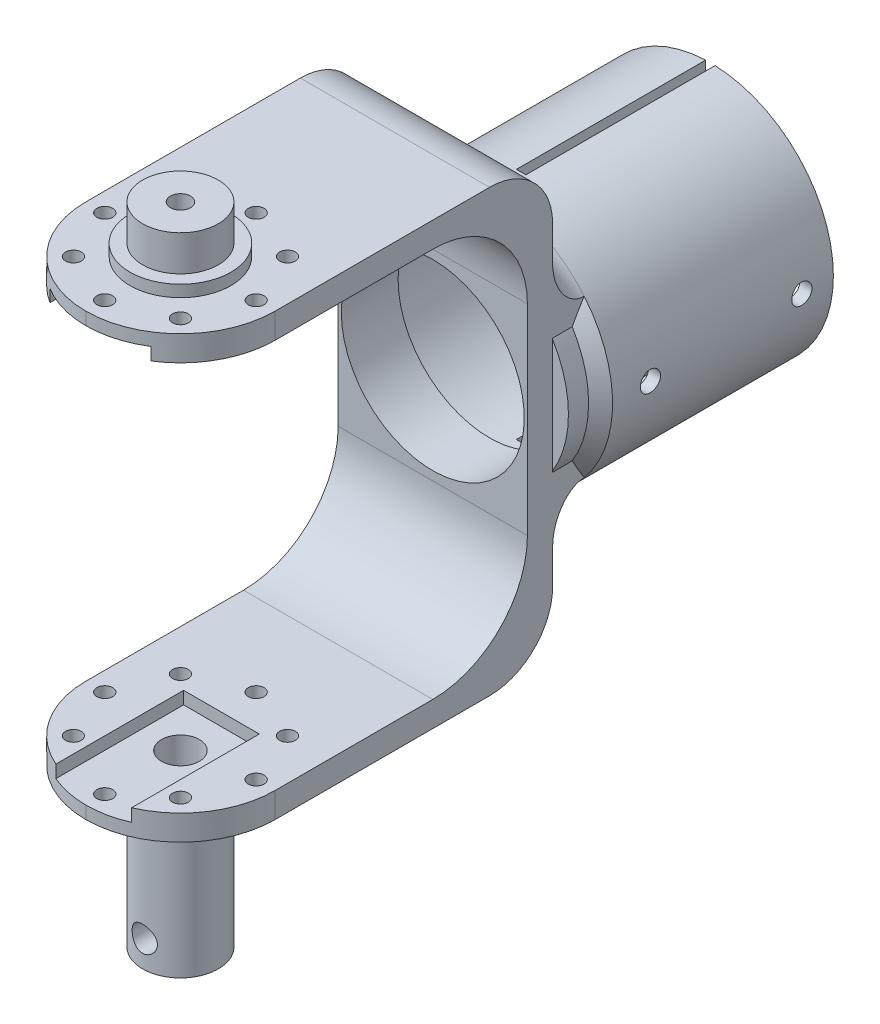
SolidWorks part; units mm, degrees
ref_plane "前视基准面" through (0, 0, 0) normal (0, 0, 1) x (1, 0, 0)
ref_plane "上视基准面" through (0, 0, 0) normal (0, 1, 0) x (1, 0, 0)
ref_plane "右视基准面" through (0, 0, 0) normal (1, 0, 0) x (0, 0, -1)
sketch "草图1" plane through (0, 0, 0) normal (1, 0, 0) x (0, 0, -1)
  line L0 (-27.5, 34.9) -> (31.5, 34.9)
  line L1 (-27.5, 30.9) -> (27.5, 30.9)
  line L2 (31.5, 34.9) -> (31.5, -34.9)
  line L3 (-27.5, -30.9) -> (27.5, -30.9)
  line L4 (27.5, 30.9) -> (27.5, -30.9)
  line L5 (-27.5, 30.9) -> (27.5, -30.9) construction
  line L6 (-27.5, -30.9) -> (27.5, 30.9) construction
  line L7 (-27.5, -34.9) -> (31.5, -34.9)
  line L8 (-27.5, 34.9) -> (-27.5, 30.9)
  line L9 (-27.5, -30.9) -> (-27.5, -34.9)
  point P0 (0, 0)
  dimension "D1" = 61.8
  dimension "D2" = 55
  dimension "D4" = 55
  dimension "D3" = 4
extrude "凸台-拉伸1" add sketch "草图1" along normal blind 30
sketch "草图4" plane through (0, 34.9, 0) normal (0, 1, 0) x (1, 0, 0)
  line L0 (30, 31.5) -> (30, -27.5) construction
  line L1 (30, -27.5) -> (0, -27.5) construction
  circle A0 centre (15, -12.5) radius 12 construction
  circle A1 centre (15, -0.5) radius 1.25
  circle A2 centre (15, -12.5) radius 12 construction
  circle A3 centre (23.4853, -4.0147) radius 1.25
  circle A4 centre (15, -12.5) radius 12 construction
  circle A5 centre (27, -12.5) radius 1.25
  circle A6 centre (15, -12.5) radius 12 construction
  circle A7 centre (23.4853, -20.9853) radius 1.25
  circle A8 centre (15, -12.5) radius 12 construction
  circle A9 centre (15, -24.5) radius 1.25
  circle A10 centre (15, -12.5) radius 12 construction
  circle A11 centre (6.5147, -20.9853) radius 1.25
  circle A12 centre (15, -12.5) radius 12 construction
  circle A13 centre (3, -12.5) radius 1.25
  circle A14 centre (15, -12.5) radius 12 construction
  circle A15 centre (6.5147, -4.0147) radius 1.25
  circle A16 centre (15, -12.5) radius 1.6
  point P31 (15, -12.5)
  dimension "D2" = 15
  dimension "D3" = 24
  dimension "D4" = 2.5
  dimension "D6" = 3.2
  dimension "D1" = 15
  dimension "D5" = 8
extrude "切除-拉伸1" cut sketch "草图4" against normal through all
fillet "圆角1" radius 15 6 edges at (0, 32.9, 27.5) (30, 32.9, 27.5) (30, -32.9, 27.5) (0, -32.9, 27.5) (15, -30.9, -27.5) (15, 30.9, -27.5)
fillet "圆角2" radius 10 2 edges at (15, -34.9, -31.5) (15, 34.9, -31.5)
sketch "草图5" plane through (0, 0, -31.5) normal (0, 0, -1) x (-1, 0, 0)
  line L0 (-30, -24.9) -> (-30, 24.9) construction
  circle A0 centre (-15, 0) radius 17.6
  circle A1 centre (-15, 0) radius 19.5
  dimension "D2" = 35.2
  dimension "D3" = 39
  dimension "D1" = 15
extrude "凸台-拉伸2" add sketch "草图5" along normal blind 40
sketch "草图7" plane through (0, 0, -71.5) normal (0, 0, -1) x (-1, 0, 0)
  line L1 (-15.75, 42.3131) -> (-14.25, 42.3131)
  line L2 (-15.75, 42.3131) -> (-15.75, -42.3131)
  line L3 (-15.75, -42.3131) -> (-14.25, -42.3131)
  line L4 (-14.25, 42.3131) -> (-14.25, -42.3131)
  line L5 (-15.75, 42.3131) -> (-14.25, -42.3131) construction
  line L6 (-15.75, -42.3131) -> (-14.25, 42.3131) construction
  point P0 (-15, 0)
  dimension "D1" = 1.5
extrude "切除-拉伸3" cut sketch "草图7" against normal blind 30
sketch "草图8" plane through (0, 0, 0) normal (1, 0, 0) x (0, 0, -1)
  line L0 (-977.5, 0) -> (49022.5, 0) construction
  line L1 (27.5, 15.9) -> (27.5, -15.9) construction
  line L2 (71.5, -19.4856) -> (71.5, 19.4856) construction
  line L3 (27.5, 15.9) -> (27.5, -15.9) construction
  circle A0 centre (66.5, 0) radius 1.6
  circle A1 centre (42.5, 0) radius 1.6
  point P5 (27.5, 0)
  dimension "D1" = 3.2
  dimension "D2" = 15
  dimension "D3" = 5
  dimension "D4" = 3.2
extrude "切除-拉伸4" cut sketch "草图8" along normal through all and the other way blind 8
sketch "草图10" plane through (0, 0, -31.5) normal (0, 0, -1) x (-1, 0, 0)
  circle A0 centre (-15, 0) radius 17.5
extrude "凸台-拉伸4" add sketch "草图10" along normal blind 5
chamfer "倒角2" distance 5 angle 45 2 edges at (34.5, 0, -31.5) (-4.5, 0, -31.5)
sketch "草图11" plane through (0, -34.9, 0) normal (0, -1, 0) x (1, 0, 0)
  circle A0 centre (15, 12.5) radius 8
  circle A1 centre (15, 12.5) radius 3
  dimension "D1" = 16
  dimension "D2" = 6
extrude "凸台-拉伸5" add sketch "草图11" along normal blind 25
sketch "草图12" plane through (0, -59.9, 0) normal (0, -1, 0) x (1, 0, 0)
  circle A0 centre (15, 12.5) radius 6
  dimension "D1" = 12
extrude "切除-拉伸5" cut sketch "草图12" against normal blind 23.15 flip side to cut
sketch "草图15" plane through (0, 34.9, 0) normal (0, 1, 0) x (1, 0, 0)
  circle A0 centre (15, -12.5) radius 8
  circle A1 centre (15, -12.5) radius 1.6
  dimension "D1" = 16
  dimension "D2" = 3.2
extrude "凸台-拉伸6" add sketch "草图15" along normal blind 7.5
sketch "草图16" plane through (0, 42.4, 0) normal (0, 1, 0) x (1, 0, 0)
  circle A0 centre (15, -12.5) radius 6
  dimension "D1" = 12
extrude "切除-拉伸6" cut sketch "草图16" against normal blind 5.65 flip side to cut
fillet "圆角3" radius 5 2 edges at (15, 19.5, -31.5) (15, -19.5, -31.5)
sketch "草图17" plane through (0, -34.9, 0) normal (0, -1, 0) x (1, 0, 0)
  circle A0 centre (15, 12.5) radius 3 construction
  circle A1 centre (15, 12.5) radius 3
extrude "切除-拉伸7" cut sketch "草图17" against normal blind 8
ref_plane "基准面1" through (0, 0, 12.5) normal (0, 0, -1) x (-1, 0, 0)
sketch "草图19" plane through (0, 0, 12.5) normal (0, 0, -1) x (-1, 0, 0)
  line L0 (0, 30.9) -> (-30, 30.9) construction
  line L1 (-7, 32.9) -> (-23, 32.9)
  line L2 (-7, 32.9) -> (-7, 28.9)
  line L3 (-7, 28.9) -> (-23, 28.9)
  line L4 (-23, 32.9) -> (-23, 28.9)
  line L5 (-7, 32.9) -> (-23, 28.9) construction
  line L6 (-7, 28.9) -> (-23, 32.9) construction
  line L7 (-30, -30.9) -> (0, -30.9) construction
  line L8 (-9, -32.9) -> (-21, -32.9)
  line L9 (-9, -32.9) -> (-9, -28.9)
  line L10 (-9, -28.9) -> (-21, -28.9)
  line L11 (-21, -32.9) -> (-21, -28.9)
  line L12 (-9, -32.9) -> (-21, -28.9) construction
  line L13 (-9, -28.9) -> (-21, -32.9) construction
  point P0 (-15, 30.9)
  point P7 (-15, -30.9)
  dimension "D1" = 12
  dimension "D2" = 4
  dimension "D3" = 16
  dimension "D4" = 4
extrude "切除-拉伸8" cut sketch "草图19" against normal blind 20 and the other way blind 6.5
sketch "草图20" plane through (0, 0, -36.5) normal (0, 0, -1) x (-1, 0, 0)
  circle A2 centre (-15, 0) radius 14.5
  circle A3 centre (-15, 0) radius 14.5
  dimension "D1" = 3
extrude "切除-拉伸9" cut sketch "草图20" against normal blind 20
ref_axis "基准轴1" through (15, -59.9, 12.5) along (0, 1, 0)
ref_plane "基准面2" through (1.25, 0, -1.25) normal (-0.7071, 0, 0.7071) x (0, 1, 0)
ref_plane "基准面3" through (0, -51.75, 0) normal (0, -1, 0) x (-1, 0, 0)
sketch "草图21" plane through (0, -51.75, 0) normal (0, -1, 0) x (-1, 0, 0)
  line L0 (-15, -12.5) -> (-15, 15.533)
  line L1 (-15, -12.5) -> (-33.3603, 9.381)
  dimension "D1" = 40
ref_plane "基准面4" through (33.3603, -51.75, -9.381) normal (0.6428, 0, -0.766) x (-0.766, 0, -0.6428)
sketch "草图22" plane through (33.3603, -51.75, -9.381) normal (0.6428, 0, -0.766) x (-0.766, 0, -0.6428)
  circle A0 centre (0, 0) radius 2
  dimension "D1" = 4
extrude "切除-拉伸10" [suppressed] cut sketch "草图22" against normal through all
ref_plane "基准面5" through (0, -55.75, 0) normal (0, -1, 0) x (-1, 0, 0)
sketch "草图24" plane through (0, -55.75, 0) normal (0, -1, 0) x (-1, 0, 0)
  line L0 (-15, -12.5) -> (-15, 15.533) construction
  line L1 (-15, -12.5) -> (-15, 15.533)
ref_plane "基准面6" through (15, -51.75, -15.533) normal (0, 0, -1) x (-1, 0, 0)
sketch "草图25" plane through (15, -51.75, -15.533) normal (0, 0, -1) x (-1, 0, 0)
  circle A0 centre (0, -4) radius 2
  dimension "D1" = 4
extrude "切除-拉伸11" cut sketch "草图25" against normal through all
